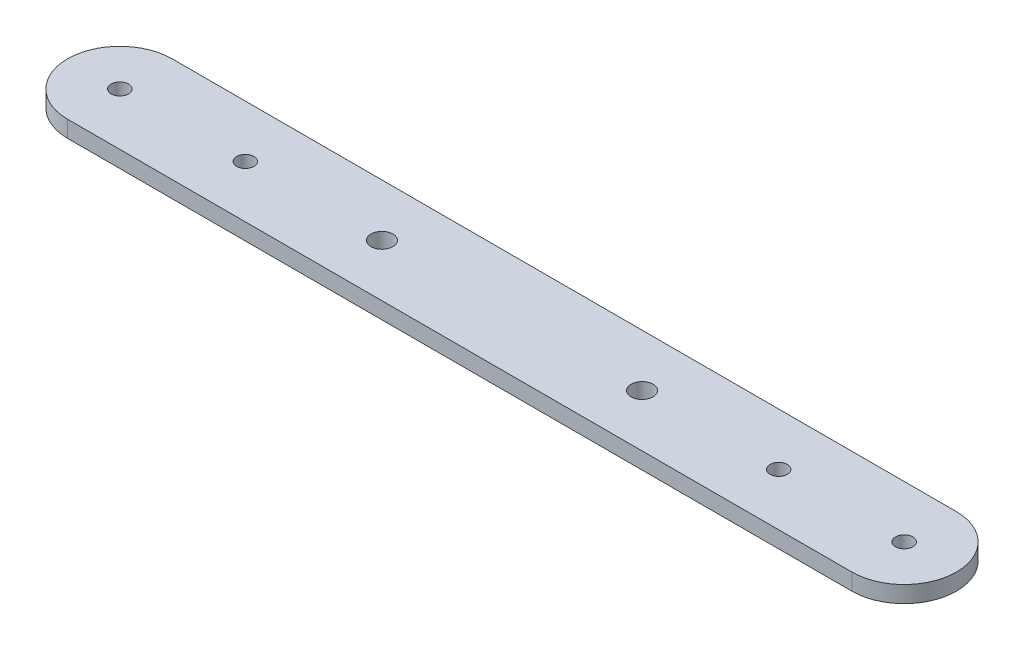
SolidWorks part; units mm, degrees
ref_plane "Front Plane" through (0, 0, 0) normal (0, 0, 1) x (1, 0, 0)
ref_plane "Top Plane" through (0, 0, 0) normal (0, 1, 0) x (1, 0, 0)
ref_plane "Right Plane" through (0, 0, 0) normal (1, 0, 0) x (0, 0, -1)
sketch "Sketch1" plane through (0, 0, 0) normal (0, 1, 0) x (1, 0, 0)
  line L0 (-85, -2.5) -> (85, -2.5) construction
  line L1 (-75, 7.5) -> (75, 7.5)
  line L3 (-75, -12.5) -> (75, -12.5)
  line L7 (0, 7.5) -> (0, -12.5) construction
  arc A0 (-75, 7.5) -> (-75, -12.5) centre (-75, -2.5) ccw
  arc A1 (75, -12.5) -> (75, 7.5) centre (75, -2.5) ccw
  circle A10 centre (-51, -2.5) radius 1.65
  circle A11 centre (51, -2.5) radius 1.65
  circle A12 centre (75, -2.5) radius 1.65
  circle A13 centre (24.8747, -2.5) radius 2.1
  circle A14 centre (-24.8747, -2.5) radius 2.1
  circle A15 centre (-75, -2.5) radius 1.65
  point P0 (0, 0)
  dimension "D9" = 4.2
  dimension "D7" = 3.3
  dimension "D3" = 4.2
  dimension "D2" = 24
  dimension "D4" = 20
  dimension "D5" = 150
  dimension "D8" = 24
  dimension "D10" = 25
  dimension "D12" = 0
  dimension "D13" = 0
extrude "Boss-Extrude1" add sketch "Sketch1" along normal blind 3.175
